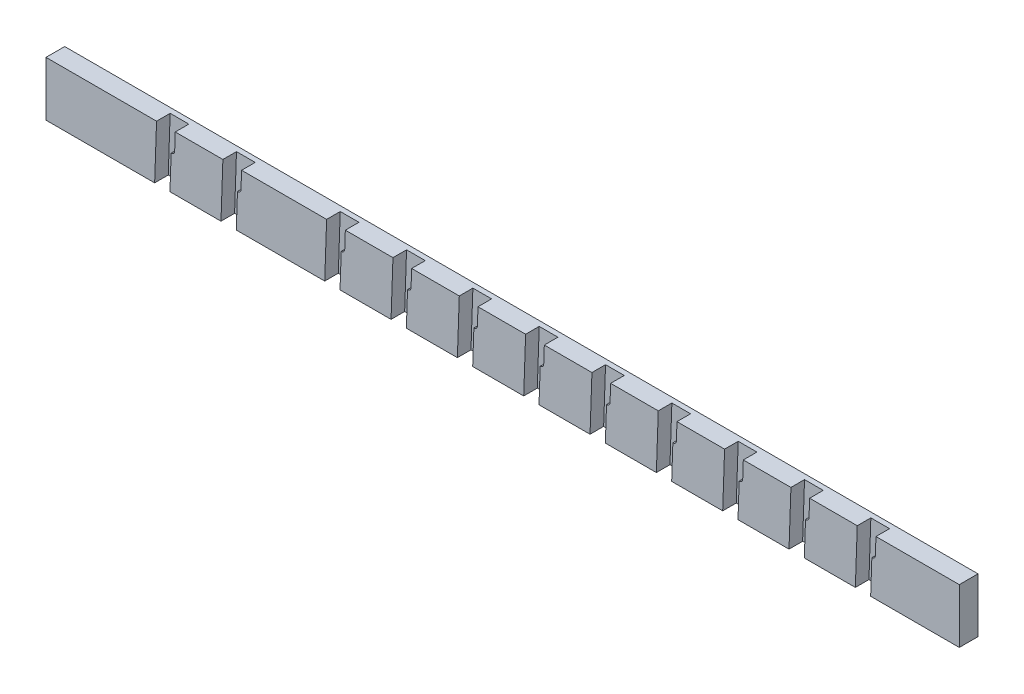
SolidWorks part; units mm, degrees
ref_plane "Front Plane" through (0, 0, 0) normal (0, 0, 1) x (1, 0, 0)
ref_plane "Top Plane" through (0, 0, 0) normal (0, 1, 0) x (1, 0, 0)
ref_plane "Right Plane" through (0, 0, 0) normal (1, 0, 0) x (0, 0, -1)
sketch "Sketch1" plane through (0, 0, 0) normal (0, 0, 1) x (1, 0, 0)
  line L1 (852.4875, 50.8) -> (-852.4875, 50.8)
  line L2 (852.4875, 50.8) -> (852.4875, -50.8)
  line L3 (852.4875, -50.8) -> (-852.4875, -50.8)
  line L4 (-852.4875, 50.8) -> (-852.4875, -50.8)
  line L5 (852.4875, 50.8) -> (-852.4875, -50.8) construction
  line L6 (852.4875, -50.8) -> (-852.4875, 50.8) construction
  point P0 (0, 0)
  dimension "D1" = 1704.975
  dimension "D2" = 101.6
extrude "Boss-Extrude1" add sketch "Sketch1" along normal blind 34.925
sketch "Sketch2" plane through (0, 0, 34.925) normal (0, 0, 1) x (1, 0, 0)
  line L0 (782.2645, -50.8) -> (785.8125, 50.8)
  line L1 (852.4875, 50.8) -> (-852.4875, 50.8) construction
  line L2 (-852.4875, -50.8) -> (852.4875, -50.8) construction
  line L3 (782.2645, -50.8) -> (810.8395, -50.8)
  line L4 (810.8395, -50.8) -> (813.057, 12.7)
  line L5 (813.057, 12.7) -> (813.2749, 12.7)
  line L6 (819.621, 18.8284) -> (820.7375, 50.8)
  line L7 (820.7375, 50.8) -> (785.8125, 50.8)
  line L8 (658.4395, -50.8) -> (661.9875, 50.8)
  line L9 (658.4395, -50.8) -> (687.0145, -50.8)
  line L10 (687.0145, -50.8) -> (689.232, 12.7)
  line L11 (689.232, 12.7) -> (689.4499, 12.7)
  line L12 (695.796, 18.8284) -> (696.9125, 50.8)
  line L13 (696.9125, 50.8) -> (661.9875, 50.8)
  line L14 (534.6145, -50.8) -> (538.1625, 50.8)
  line L15 (534.6145, -50.8) -> (563.1895, -50.8)
  line L16 (563.1895, -50.8) -> (565.407, 12.7)
  line L17 (565.407, 12.7) -> (565.6249, 12.7)
  line L18 (571.971, 18.8284) -> (573.0875, 50.8)
  line L19 (573.0875, 50.8) -> (538.1625, 50.8)
  line L20 (410.7895, -50.8) -> (414.3375, 50.8)
  line L21 (410.7895, -50.8) -> (439.3645, -50.8)
  line L22 (439.3645, -50.8) -> (441.582, 12.7)
  line L23 (441.582, 12.7) -> (441.7999, 12.7)
  line L24 (448.146, 18.8284) -> (449.2625, 50.8)
  line L25 (449.2625, 50.8) -> (414.3375, 50.8)
  line L26 (286.9645, -50.8) -> (290.5125, 50.8)
  line L27 (286.9645, -50.8) -> (315.5395, -50.8)
  line L28 (315.5395, -50.8) -> (317.757, 12.7)
  line L29 (317.757, 12.7) -> (317.9749, 12.7)
  line L30 (324.321, 18.8284) -> (325.4375, 50.8)
  line L31 (325.4375, 50.8) -> (290.5125, 50.8)
  line L32 (163.1395, -50.8) -> (166.6875, 50.8)
  line L33 (163.1395, -50.8) -> (191.7145, -50.8)
  line L34 (191.7145, -50.8) -> (193.932, 12.7)
  line L35 (193.932, 12.7) -> (194.1499, 12.7)
  line L36 (200.496, 18.8284) -> (201.6125, 50.8)
  line L37 (201.6125, 50.8) -> (166.6875, 50.8)
  line L38 (39.3145, -50.8) -> (42.8625, 50.8)
  line L39 (39.3145, -50.8) -> (67.8895, -50.8)
  line L40 (67.8895, -50.8) -> (70.107, 12.7)
  line L41 (70.107, 12.7) -> (70.3249, 12.7)
  line L42 (76.671, 18.8284) -> (77.7875, 50.8)
  line L43 (77.7875, 50.8) -> (42.8625, 50.8)
  line L44 (-84.5105, -50.8) -> (-80.9625, 50.8)
  line L45 (-84.5105, -50.8) -> (-55.9355, -50.8)
  line L46 (-55.9355, -50.8) -> (-53.718, 12.7)
  line L47 (-53.718, 12.7) -> (-53.5001, 12.7)
  line L48 (-47.154, 18.8284) -> (-46.0375, 50.8)
  line L49 (-46.0375, 50.8) -> (-80.9625, 50.8)
  line L50 (-208.3355, -50.8) -> (-204.7875, 50.8)
  line L51 (-208.3355, -50.8) -> (-179.7605, -50.8)
  line L52 (-179.7605, -50.8) -> (-177.543, 12.7)
  line L53 (-177.543, 12.7) -> (-177.3251, 12.7)
  line L54 (-170.979, 18.8284) -> (-169.8625, 50.8)
  line L55 (-169.8625, 50.8) -> (-204.7875, 50.8)
  line L56 (-332.1605, -50.8) -> (-328.6125, 50.8)
  line L57 (-332.1605, -50.8) -> (-303.5855, -50.8)
  line L58 (-303.5855, -50.8) -> (-301.368, 12.7)
  line L59 (-301.368, 12.7) -> (-301.1501, 12.7)
  line L60 (-294.804, 18.8284) -> (-293.6875, 50.8)
  line L61 (-293.6875, 50.8) -> (-328.6125, 50.8)
  line L62 (-852.4875, 50.8) -> (-852.4875, -50.8) construction
  line L63 (-525.8355, -50.8) -> (-522.2875, 50.8)
  line L64 (-525.8355, -50.8) -> (-497.2605, -50.8)
  line L65 (-497.2605, -50.8) -> (-495.043, 12.7)
  line L66 (-495.043, 12.7) -> (-494.8251, 12.7)
  line L67 (-488.479, 18.8284) -> (-487.3625, 50.8)
  line L68 (-487.3625, 50.8) -> (-522.2875, 50.8)
  line L69 (-649.6605, -50.8) -> (-646.1125, 50.8)
  line L70 (-649.6605, -50.8) -> (-621.0855, -50.8)
  line L71 (-621.0855, -50.8) -> (-618.868, 12.7)
  line L72 (-618.868, 12.7) -> (-618.6501, 12.7)
  line L73 (-612.304, 18.8284) -> (-611.1875, 50.8)
  line L74 (-611.1875, 50.8) -> (-646.1125, 50.8)
  line L75 (-773.4855, -50.8) -> (-769.9375, 50.8)
  line L76 (-773.4855, -50.8) -> (-744.9105, -50.8)
  line L77 (-744.9105, -50.8) -> (-742.693, 12.7)
  line L78 (-742.693, 12.7) -> (-742.4751, 12.7)
  line L79 (-736.129, 18.8284) -> (-735.0125, 50.8)
  line L80 (-735.0125, 50.8) -> (-769.9375, 50.8)
  arc A0 (813.2749, 12.7) -> (819.621, 18.8284) centre (813.2749, 19.05) ccw
  arc A1 (689.4499, 12.7) -> (695.796, 18.8284) centre (689.4499, 19.05) ccw
  arc A2 (565.6249, 12.7) -> (571.971, 18.8284) centre (565.6249, 19.05) ccw
  arc A3 (441.7999, 12.7) -> (448.146, 18.8284) centre (441.7999, 19.05) ccw
  arc A4 (317.9749, 12.7) -> (324.321, 18.8284) centre (317.9749, 19.05) ccw
  arc A5 (194.1499, 12.7) -> (200.496, 18.8284) centre (194.1499, 19.05) ccw
  arc A6 (70.3249, 12.7) -> (76.671, 18.8284) centre (70.3249, 19.05) ccw
  arc A7 (-53.5001, 12.7) -> (-47.154, 18.8284) centre (-53.5001, 19.05) ccw
  arc A8 (-177.3251, 12.7) -> (-170.979, 18.8284) centre (-177.3251, 19.05) ccw
  arc A9 (-301.1501, 12.7) -> (-294.804, 18.8284) centre (-301.1501, 19.05) ccw
  arc A10 (-494.8251, 12.7) -> (-488.479, 18.8284) centre (-494.8251, 19.05) ccw
  arc A11 (-618.6501, 12.7) -> (-612.304, 18.8284) centre (-618.6501, 19.05) ccw
  arc A12 (-742.4751, 12.7) -> (-736.129, 18.8284) centre (-742.4751, 19.05) ccw
  line M6 (-852.4875, -50.8) -> (852.4875, -50.8)
  line M8 (852.4875, 50.8) -> (-852.4875, 50.8)
  dimension "D6" = 6.35
  dimension "D1" = 34.925
  dimension "D2" = 38.1
  dimension "D3" = 28.575
  dimension "D4" = 88
  dimension "D5" = 31.75
  dimension "D8" = 520.327
  dimension "D9" = 2
  dimension "D10" = 326.652
  dimension "D11" = 63.5
  dimension "D12" = 3
  dimension "D13" = 79.002
  dimension "D14" = 101.6
  dimension "D17" = 1704.975
  dimension "D29" = 1704.975
  dimension "D7" = 10
extrude "Cut-Extrude1" cut sketch "Sketch2" against normal blind 25.4 contours L11 A1 L12 L8 L10 M8 M6 | L17 A2 L18 L14 L16 M8 M6 | L23 A3 L24 L20 L22 M8 M6 | L29 A4 L30 L26 L28 M8 M6 | L35 A5 L36 L32 L34 M8 M6 | L41 A6 L42 L38 L40 M8 M6 | L47 A7 L48 L44 L46 M8 M6 | L53 A8 L54 L50 L52 M8 M6 | L66 A10 L67 L63 L65 M8 M6 | L72 A11 L73 L69 L71 M8 M6 | L56 L61 L60 A9 L59 L58 L57 region at (675.883, 2.4128, 34.925) region at (552.058, 2.4128, 34.925) region at (428.233, 2.4128, 34.925) region at (304.408, 2.4128, 34.925) region at (180.583, 2.4128, 34.925) region at (56.758, 2.4128, 34.925) region at (-67.067, 2.4128, 34.925) region at (-190.892, 2.4128, 34.925) region at (-508.392, 2.4128, 34.925) region at (-632.217, 2.4128, 34.925)
sketch "Sketch3" plane through (0, 0, 0) normal (0, 0, -1) x (-1, 0, 0)
  line L0 (852.4875, -50.8) -> (-852.4875, -50.8) construction
  line L1 (827.0875, -50.8) -> (741.3625, -50.8)
  line L2 (827.0875, -50.8) -> (827.0875, -25.4)
  line L3 (827.0875, -25.4) -> (741.3625, -25.4)
  line L4 (741.3625, -50.8) -> (741.3625, -25.4)
  line L5 (852.4875, 50.8) -> (852.4875, -50.8) construction
  line L6 (-366.7125, -25.4) -> (-452.4375, -25.4)
  line L7 (-452.4375, -25.4) -> (-452.4375, -50.8)
  line L8 (-452.4375, -50.8) -> (-366.7125, -50.8)
  line L9 (-366.7125, -50.8) -> (-366.7125, -25.4)
  dimension "D1" = 25.4
  dimension "D2" = 85.725
  dimension "D3" = 1108.075
  dimension "D4" = 85.725
  dimension "D5" = 25.4
  dimension "D6" = 25.4
